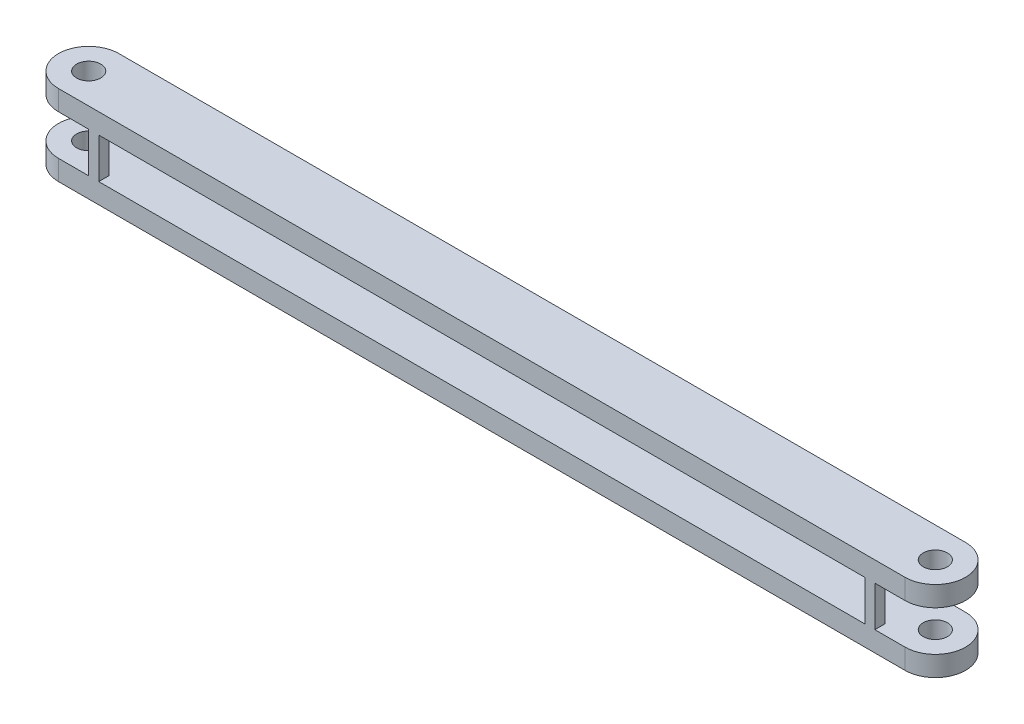
SolidWorks part; units mm, degrees
ref_plane "前视基准面" through (0, 0, 0) normal (0, 0, 1) x (1, 0, 0)
ref_plane "上视基准面" through (0, 0, 0) normal (0, 1, 0) x (1, 0, 0)
ref_plane "右视基准面" through (0, 0, 0) normal (1, 0, 0) x (0, 0, -1)
sketch "草图1" plane through (0, 0, 0) normal (0, 1, 0) x (1, 0, 0)
  line L0 (-105, 0) -> (105, 0) construction
  line L1 (-105, 7.5) -> (105, 7.5)
  line L2 (-105, -7.5) -> (105, -7.5)
  arc A0 (-105, 7.5) -> (-105, -7.5) centre (-105, 0) ccw
  arc A1 (105, -7.5) -> (105, 7.5) centre (105, 0) ccw
  point P3 (0, 0)
  point P8 (0, 0)
  dimension "D1" = 210
  dimension "D2" = 15
extrude "凸台-拉伸1" add sketch "草图1" along normal blind 20
sketch "草图2" plane through (0, 0, -7.5) normal (0, 0, -1) x (-1, 0, 0)
  line L0 (0, 0) -> (0, 10) construction
  line L1 (95, 5) -> (-95, 5)
  line L2 (95, 5) -> (95, 15)
  line L3 (95, 15) -> (-95, 15)
  line L4 (-95, 5) -> (-95, 15)
  line L5 (95, 5) -> (-95, 15) construction
  line L6 (95, 15) -> (-95, 5) construction
  line L7 (-105, 0) -> (105, 0) construction
  point P0 (0, 10)
  dimension "D1" = 10
  dimension "D2" = 10
  dimension "D3" = 190
extrude "切除-拉伸3" cut sketch "草图2" against normal through all
sketch "草图3" plane through (0, 0, -7.5) normal (0, 0, -1) x (-1, 0, 0)
  line L0 (-95, 5) -> (95, 5) construction
  line L1 (112.5, 15) -> (97.5, 15)
  line L2 (112.5, 15) -> (112.5, 5)
  line L3 (112.5, 5) -> (97.5, 5)
  line L4 (97.5, 15) -> (97.5, 5)
  line L5 (95, 15) -> (-95, 15) construction
  line L6 (112.5, 0) -> (112.5, 20) construction
  line L7 (0, 0) -> (0, 43.872) construction
  line L8 (-105, 0) -> (105, 0) construction
  line L9 (-97.5, 15) -> (-97.5, 5)
  line L10 (-112.5, 5) -> (-97.5, 5)
  line L11 (-112.5, 15) -> (-112.5, 5)
  line L12 (-112.5, 15) -> (-97.5, 15)
  dimension "D1" = 15
extrude "切除-拉伸4" cut sketch "草图3" against normal through all
sketch "草图4" plane through (-97.5, 0, 0) normal (-1, 0, 0) x (0, 0, 1)
  line L0 (7.5, 5) -> (-7.5, 5) construction
  line L1 (5, 15) -> (-5, 15)
  line L2 (5, 15) -> (5, 5)
  line L3 (5, 5) -> (-5, 5)
  line L4 (-5, 15) -> (-5, 5)
  line L5 (5, 15) -> (-5, 5) construction
  line L6 (5, 5) -> (-5, 15) construction
  line L7 (0, 0) -> (0, 10) construction
  line L8 (7.5, 15) -> (-7.5, 15) construction
  point P0 (0, 10)
  dimension "D1" = 10
extrude "切除-拉伸5" cut sketch "草图4" against normal through all
sketch "草图5" plane through (0, 20, 0) normal (0, 1, 0) x (1, 0, 0)
  line L0 (-105, 0) -> (0, 0) construction
  line L1 (0, 0) -> (105, 0) construction
  circle A0 centre (-105, 0) radius 3
  circle A1 centre (105, 0) radius 3
  dimension "D1" = 6
  dimension "D2" = 6
  dimension "D3" = 105
  dimension "D4" = 105
extrude "切除-拉伸6" cut sketch "草图5" against normal through all
